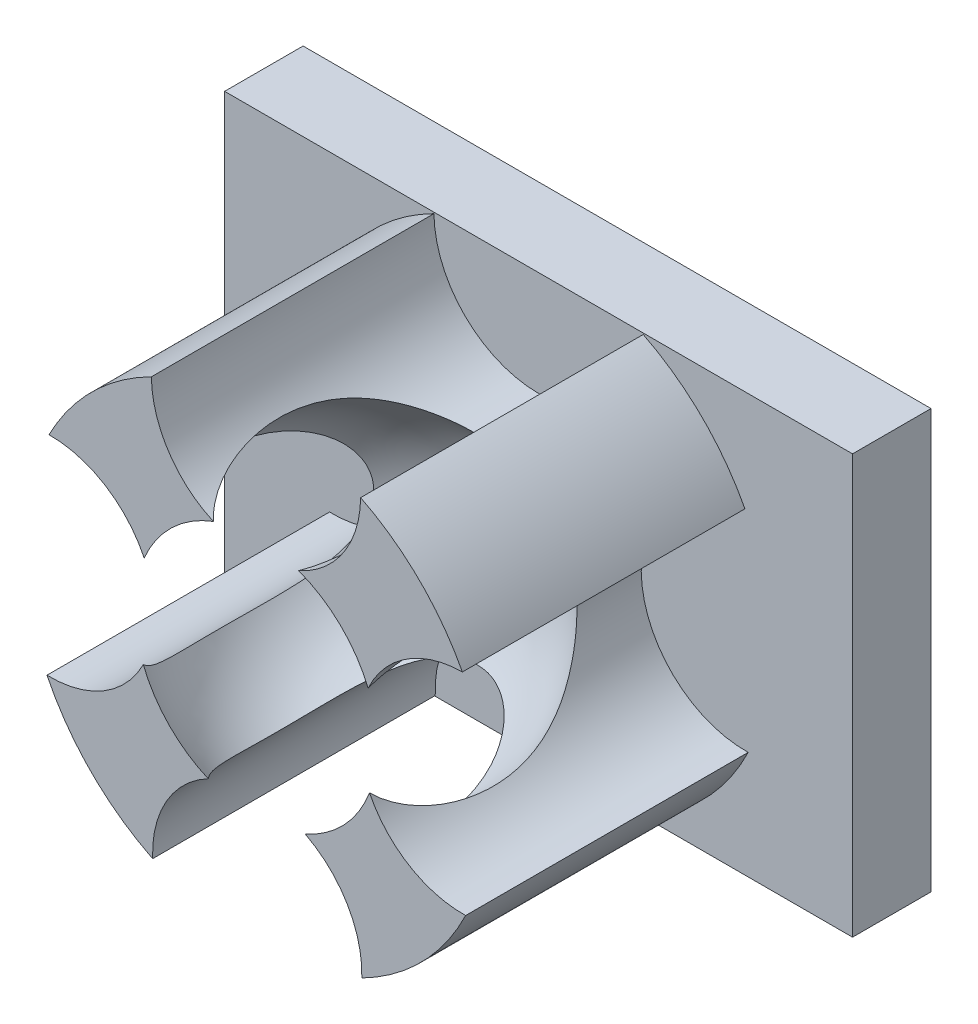
SolidWorks part; units mm, degrees
ref_plane "Ebene vorne" through (0, 0, 0) normal (0, 0, 1) x (1, 0, 0)
ref_plane "Ebene oben" through (0, 0, 0) normal (0, 1, 0) x (1, 0, 0)
ref_plane "Ebene rechts" through (0, 0, 0) normal (1, 0, 0) x (0, 0, -1)
sketch "Skizze1" plane through (0, 0, 0) normal (0, 0, 1) x (1, 0, 0)
  line L1 (12, 8) -> (-12, 8)
  line L2 (12, 8) -> (12, -8)
  line L3 (12, -8) -> (-12, -8)
  line L4 (-12, 8) -> (-12, -8)
  line L5 (12, 8) -> (-12, -8) construction
  line L6 (12, -8) -> (-12, 8) construction
  point P0 (0, 0)
  dimension "D1" = 24
  dimension "D2" = 16
extrude "Aufsatz-Linear austragen1" add sketch "Skizze1" along normal blind 3
sketch "Skizze2" plane through (0, 0, 3) normal (0, 0, 1) x (1, 0, 0)
  line L0 (0, 0) -> (0, 8) construction
  arc A0 (-3.9997, 7.9506) -> (-7.9113, 4.077) centre (0, 0) ccw
  arc A1 (-3.9997, 7.9506) -> (3.9997, 7.9506) centre (0, 8) ccw
  arc A2 (7.8872, 4.1233) -> (8.0119, -3.8755) centre (7.9228, 0.1235) ccw
  arc A3 (4.0442, -7.9281) -> (-3.9498, -7.9755) centre (0.0463, -7.7994) ccw
  arc A4 (-7.9896, -3.9212) -> (-7.9113, 4.077) centre (-7.8765, 0.0772) ccw
  arc A5 (7.8872, 4.1233) -> (3.9997, 7.9506) centre (0, 0) ccw
  arc A6 (4.0442, -7.9281) -> (8.0119, -3.8755) centre (0, 0) ccw
  arc A7 (-7.9896, -3.9212) -> (-3.9498, -7.9755) centre (0, 0) ccw
  point P14 (0.0231, 0.1003)
  dimension "D1" = 17.8
  dimension "D2" = 8
  dimension "D3" = 8
  dimension "D4" = 4
extrude "Aufsatz-Linear austragen2" add sketch "Skizze2" along normal blind 10.8
sketch "Skizze3" plane through (0, 0, 0) normal (0, 1, 0) x (1, 0, 0)
  line L0 (0, -4) -> (0, -10) construction
  line L1 (0, -10) -> (0, -16) construction
  line L2 (12, 0) -> (-12, 0) construction
  line L3 (0, -4) -> (0, -16)
  arc A0 (0, -16) -> (0, -4) centre (0, -10) ccw
  dimension "D1" = 6
  dimension "D2" = 16
revolve "Schnitt-Rotation1" cut sketch "Skizze3" angle 360 about L3
